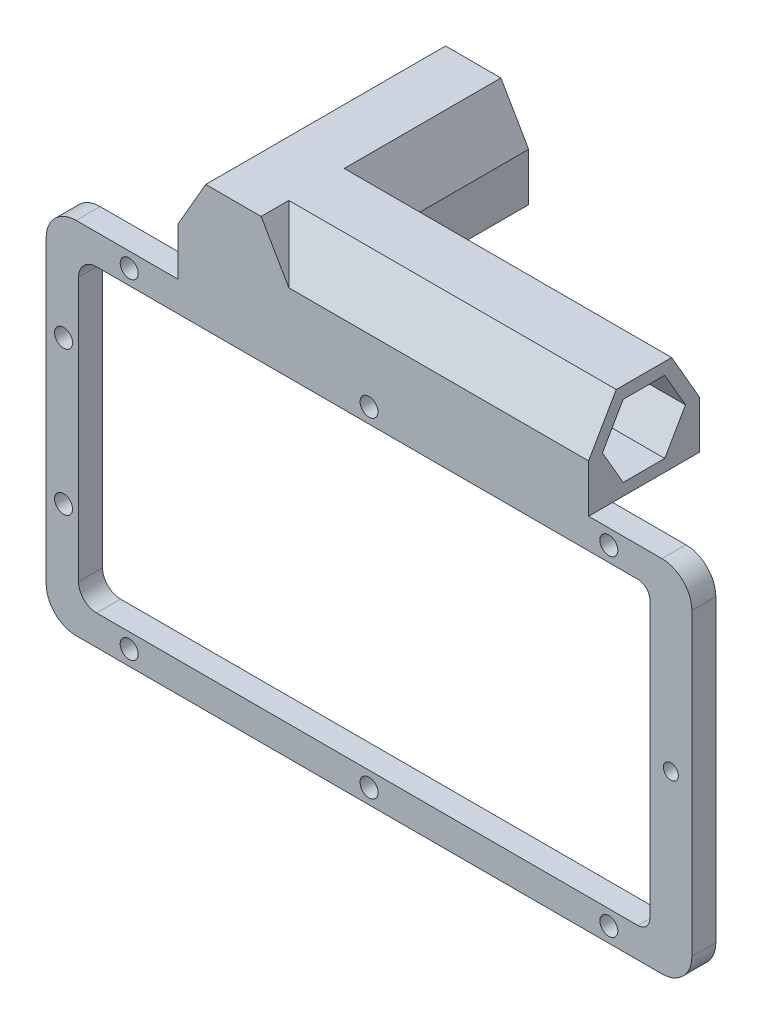
SolidWorks part; units mm, degrees
ref_plane "Front Plane" through (0, 0, 0) normal (0, 0, 1) x (1, 0, 0)
ref_plane "Top Plane" through (0, 0, 0) normal (0, 1, 0) x (1, 0, 0)
ref_plane "Right Plane" through (0, 0, 0) normal (1, 0, 0) x (0, 0, -1)
sketch "Sketch3" plane through (0, 0, 0) normal (0, 0, 1) x (1, 0, 0)
  line L8 (-48.15, 22) -> (-48.15, -22)
  line L9 (45.15, 25) -> (-45.15, 25)
  line L10 (47.15, -23) -> (47.15, 23)
  line L11 (-45.15, -25) -> (45.15, -25)
  line L16 (-53.55, 25) -> (-53.55, -25)
  line L17 (-48.55, -30) -> (49.15, -30)
  line L18 (54.15, -25) -> (54.15, 25)
  line L19 (49.15, 30) -> (-48.55, 30)
  circle A2 centre (-39.7, 27.5) radius 1.5
  arc A8 (-45.15, 25) -> (-48.15, 22) centre (-45.15, 22) ccw
  arc A9 (47.15, 23) -> (45.15, 25) centre (45.15, 23) ccw
  arc A10 (45.15, -25) -> (47.15, -23) centre (45.15, -23) ccw
  arc A11 (-48.15, -22) -> (-45.15, -25) centre (-45.15, -22) ccw
  circle A12 centre (40.3, 27.5) radius 1.5
  circle A14 centre (40.3, -27.5) radius 1.5
  circle A16 centre (0.3, -27.5) radius 1.5
  circle A18 centre (-50.65, -12) radius 1.5
  circle A20 centre (-50.65, 12) radius 1.5
  circle A22 centre (-39.7, -27.5) radius 1.5
  circle A24 centre (0.3, 27.5) radius 1.5
  circle A26 centre (50.65, 0) radius 1.25
  arc A34 (-53.55, -25) -> (-48.55, -30) centre (-48.55, -25) ccw
  arc A35 (49.15, -30) -> (54.15, -25) centre (49.15, -25) ccw
  arc A36 (54.15, 25) -> (49.15, 30) centre (49.15, 25) ccw
  arc A37 (-48.55, 30) -> (-53.55, 25) centre (-48.55, 25) ccw
  point P14 (0, 0)
  point P21 (0, 25)
  point P24 (-48.15, 0)
extrude "Boss-Extrude1" add sketch "Sketch3" along normal blind 4
sketch "Sketch5" plane through (0, 0, 4) normal (0, 0, 1) x (1, 0, 0)
  line L8 (49.15, 30) -> (-48.55, 30) construction
  line L10 (-13.0748, 38) -> (-17.6936, 46)
  line L17 (-17.6936, 46) -> (-26.9312, 46)
  line L18 (-26.9312, 46) -> (-31.55, 38)
  line L19 (-31.55, 38) -> (-26.9312, 30)
  line L20 (-26.9312, 30) -> (-17.6936, 30)
  line L21 (-17.6936, 30) -> (-13.0748, 38)
  line L22 (-31.55, 38) -> (-31.55, 30)
  line L23 (-31.55, 30) -> (-26.9312, 30)
  line L24 (-17.6936, 30) -> (-13.0748, 30)
  line L25 (-13.0748, 30) -> (-13.0748, 38)
  line L26 (-53.55, 25) -> (-53.55, -25) construction
  line L28 (-15.3842, 38) -> (-18.8483, 44)
  line L29 (-18.8483, 44) -> (-25.7765, 44)
  line L30 (-25.7765, 44) -> (-29.2406, 38)
  line L31 (-29.2406, 38) -> (-25.7765, 32)
  line L32 (-25.7765, 32) -> (-18.8483, 32)
  line L33 (-18.8483, 32) -> (-15.3842, 38)
  circle A0 centre (-22.3124, 38) radius 8 construction
  circle A1 centre (-22.3124, 38) radius 6 construction
  line M26 (49.15, 30) -> (-48.55, 30)
  dimension "D1" = 22
  dimension "D2" = 2
  dimension "D3" = 12
extrude "Boss-Extrude2" add sketch "Sketch5" against normal blind 40 contours L31 L30 L10 L17 L18 L19 L29 L28 M26 | L19 L22 M26 | L25 L21 M26 region at (-15.5959, 34.1222, 4) region at (-14.6144, 32.6667, 4) region at (-30.0104, 32.6667, 4)
sketch "Sketch8" plane through (-13.0748, 0, 0) normal (1, 0, 0) x (0, 0, -1)
  line L0 (-4, 30) -> (-4, 38) construction
  line L1 (14.4752, 38) -> (9.8564, 46)
  line L2 (9.8564, 46) -> (0.6188, 46)
  line L3 (0.6188, 46) -> (-4, 38)
  line L4 (-4, 38) -> (0.6188, 30)
  line L5 (0.6188, 30) -> (9.8564, 30)
  line L6 (9.8564, 30) -> (14.4752, 38)
  line L7 (36, 30) -> (0, 30) construction
  line L8 (36, 46) -> (-4, 46) construction
  line L9 (-4, 38) -> (-4, 30)
  line L10 (12.1658, 38) -> (8.7017, 44)
  line L11 (8.7017, 44) -> (1.7735, 44)
  line L12 (1.7735, 44) -> (-1.6906, 38)
  line L13 (-1.6906, 38) -> (1.7735, 32)
  line L14 (1.7735, 32) -> (8.7017, 32)
  line L15 (8.7017, 32) -> (12.1658, 38)
  line L16 (-4, 30) -> (0.6188, 30)
  line L17 (9.8564, 30) -> (14.4752, 30)
  line L18 (14.4752, 30) -> (14.4752, 38)
  circle A0 centre (5.2376, 38) radius 8 construction
  circle A1 centre (5.2376, 38) radius 6 construction
  line M4 (-4, 38) -> (-4, 30)
  line M5 (-4, 30) -> (0, 30)
  line M6 (0, 30) -> (36, 30)
  line M8 (36, 38) -> (-4, 38)
  dimension "D1" = 2
extrude "Boss-Extrude5" add sketch "Sketch8" along normal blind 50 contours L4 M4 M5 M6 | L15 L14 L13 L4 L6 M8 M6 | L18 L6 M6 | L12 L11 L10 L1 L2 L3 M8 region at (-13.0748, 38.2013, -13.3205) region at (-13.0748, 32.6667, -12.9356) region at (-13.0748, 34.1007, -11.9915) region at (-13.0748, 32.6667, 2.4604)
extrude "Boss-Extrude6" add sketch "Sketch8<3>" against normal up to surface contours L12 L11 L10 L1 L2 L3 M8 region at (-13.0748, 38.2013, -13.3205) up to face at (-14.3944, 40.2857, -12.7072)
sketch "Sketch8<3>" plane through (-13.0748, 0, 0) normal (1, 0, 0) x (0, 0, -1) same geometry as "Sketch8"
extrude "Cut-Extrude2" cut sketch "Sketch8<4>" against normal through all contours L11 L12 L10 M8 | L14 L15 L13 M8 region at (-13.0748, 40.6667, -5.2376) region at (-13.0748, 35.3333, -5.2376)
sketch "Sketch8<4>" plane through (-13.0748, 0, 0) normal (1, 0, 0) x (0, 0, -1) same geometry as "Sketch8"
extrude "Boss-Extrude7" add sketch "Sketch5<3>" against normal up to vertex (2.3094 mm away) contours L32 L33 L28 L29 L30 L31 region at (-22.3124, 38, 4) up to point (-31.55, 38, 1.6906)
sketch "Sketch5<3>" plane through (0, 0, 4) normal (0, 0, 1) x (1, 0, 0) same geometry as "Sketch5"
